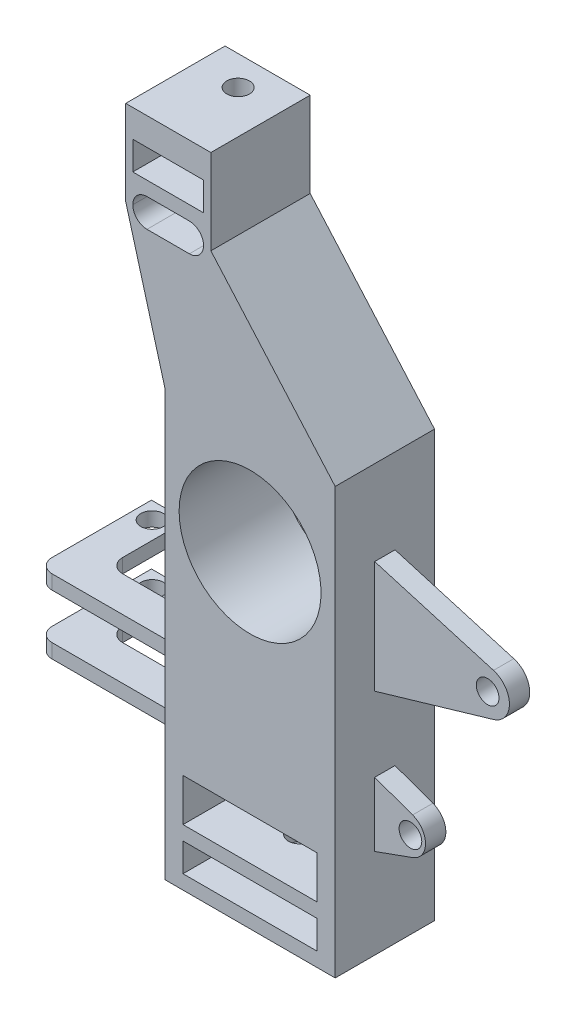
SolidWorks part; units mm, degrees
ref_plane "Front Plane" through (0, 0, 0) normal (0, 0, 1) x (1, 0, 0)
ref_plane "Top Plane" through (0, 0, 0) normal (0, 1, 0) x (1, 0, 0)
ref_plane "Right Plane" through (0, 0, 0) normal (1, 0, 0) x (0, 0, -1)
sketch "Sketch1" plane through (0, 0, 0) normal (0, 0, 1) x (1, 0, 0)
  line L3 (30, -10) -> (-30, -10)
  line L4 (0, 0) -> (0, 205)
  line L5 (0, 205) -> (-28.8109, 205) construction
  line L6 (-28.8109, 205) -> (0, 0) construction
  line L7 (30, -10) -> (30, 140)
  line L13 (-30, 140) -> (-30, -10)
  line L15 (-13.8109, 190) -> (-13.8109, 220)
  line L16 (-13.8109, 220) -> (-43.8109, 220)
  line L17 (-43.8109, 220) -> (-43.8109, 190)
  line L19 (-43.8109, 190) -> (-30, 140)
  line L20 (-13.8109, 190) -> (30, 140)
  dimension "D1" = 205
  dimension "D2" = 8
  dimension "D3" = 30
  dimension "D4" = 30
  dimension "D5" = 10
  dimension "D6" = 15
  dimension "D7" = 15
  dimension "D8" = 15
  dimension "D9" = 15
  dimension "D10" = 30
  dimension "D11" = 150
  dimension "D12" = 150
sketch "Sketch3" plane through (0, 0, 0) normal (1, 0, 0) x (0, 0, -1)
  line L0 (0, 205) -> (0, 0) construction
  line L1 (0, 205) -> (0, 0) construction
  line L2 (7.1588, 205) -> (0, 0) construction
  line L3 (0, 205) -> (7.1588, 205)
  dimension "D1" = 2
  dimension "D2" = 205
extrude "Boss-Extrude1" add sketch "Sketch1" along normal mid plane 35 contours L17 L19 L13 L3 L7 L20 L15 L16 region at (-4.5054, 93.3745, 0)
sketch "Sketch4" plane through (0, 0, 0) normal (0, 0, 1) x (1, 0, 0)
  line L0 (0, 205.3073) -> (-28.8541, 205.3073) construction
  line L1 (0, 205) -> (0, 0) construction
  line L2 (-28.8541, 205.3073) -> (0, 0) construction
  point P4 (0, 0)
  dimension "D1" = 8
sketch3d "3DSketch1"
  line L0 (0, 205, -7.1588) -> (-28.8601, 205, -7.1588) construction
  line L1 (-28.8601, 205, -7.1588) -> (-28.8265, 205.111, 0) construction
  line L2 (-28.8541, 205.3073, 0) -> (0, 0, 0) construction
  line L3 (0, 205, 0) -> (0, 205, -7.1588) construction
  line L4 (0, 205, -7.1588) -> (0, 0, 0) construction
  point P9 (0, 0, 0)
  point P10 (0, 0, 0)
  point P11 (0, 0, 0)
  point P12 (-28.8601, 205, -7.1588)
  point P13 (0, 0, 0)
sketch3d "3DSketch2"
  line L0 (-28.8601, 205, -7.1588) -> (0, 0, 0)
  point P4 (0, 0, 0)
sketch "Sketch6" plane through (0, 0, -17.5) normal (0, 0, -1) x (-1, 0, 0)
  line L0 (16.383, 195.3073) -> (41.3251, 195.3073)
  line L1 (23.6291, 5) -> (-23.6291, 5)
  line L2 (23.6291, 5) -> (23.6291, -5)
  line L3 (23.6291, -5) -> (-23.6291, -5)
  line L4 (-23.6291, 5) -> (-23.6291, -5)
  line L5 (23.6291, 5) -> (-23.6291, -5) construction
  line L6 (23.6291, -5) -> (-23.6291, 5) construction
  line L7 (23.6291, 25) -> (-23.6291, 25)
  line L8 (23.6291, 25) -> (23.6291, 10)
  line L9 (23.6291, 10) -> (-23.6291, 10)
  line L10 (-23.6291, 25) -> (-23.6291, 10)
  line L11 (23.6291, 25) -> (-23.6291, 10) construction
  line L12 (23.6291, 10) -> (-23.6291, 25) construction
  line L13 (41.3251, 210.3073) -> (16.383, 210.3073)
  line L14 (41.3251, 210.3073) -> (41.3251, 200.3073)
  line L15 (41.3251, 200.3073) -> (16.383, 200.3073)
  line L16 (16.383, 210.3073) -> (16.383, 200.3073)
  line L17 (41.3251, 210.3073) -> (16.383, 200.3073) construction
  line L18 (41.3251, 200.3073) -> (16.383, 210.3073) construction
  line L19 (41.3251, 195.3073) -> (41.3251, 185.3073)
  line L20 (41.3251, 185.3073) -> (16.383, 185.3073)
  line L21 (16.383, 185.3073) -> (16.383, 195.3073)
  point P0 (0, 0)
  point P6 (0, 17.5)
  point P11 (28.8541, 205.3073)
  dimension "D1" = 10
  dimension "D2" = 15
  dimension "D3" = 5
  dimension "D4" = 10
  dimension "D5" = 10
  dimension "D6" = 5
extrude "Cut-Extrude1" cut sketch "Sketch6" against normal through all
sketch "Sketch7" plane through (0, 0, -17.5) normal (0, 0, -1) x (-1, 0, 0)
  line L0 (0, 205) -> (0, 0) construction
  line L1 (-30, -10) -> (30, -10) construction
  circle A0 centre (0, 105) radius 25
  point P0 (0, 105)
  dimension "D2" = 50
  dimension "D1" = 115
extrude "Cut-Extrude2" cut sketch "Sketch7" against normal through all
sketch "Sketch8" plane through (0, 220, 0) normal (0, 1, 0) x (1, 0, 0)
  circle A0 centre (-28.8601, 7.1588) radius 4
  dimension "D1" = 8
extrude "Cut-Extrude3" cut sketch "Sketch8" against normal blind 30
sketch "Sketch10" plane through (0, -10, 0) normal (0, -1, 0) x (1, 0, 0)
  circle A0 centre (0, 0) radius 4
  dimension "D1" = 8
extrude "Cut-Extrude4" cut sketch "Sketch10" against normal blind 30
sketch "Sketch11" plane through (30, 0, 0) normal (1, 0, 0) x (0, 0, -1)
  line L1 (-3.5809, 110.12) -> (3.5794, 110.12)
  line L2 (-3.5809, 110.12) -> (-3.5809, 70.5679)
  line L3 (-3.5809, 70.5679) -> (3.5794, 70.5679)
  line L4 (3.5794, 110.12) -> (3.5794, 70.5679)
  line L5 (-3.5809, 44.2881) -> (3.5794, 44.2881)
  line L6 (-3.5809, 44.2881) -> (-3.5809, 21.6508)
  line L7 (-3.5809, 21.6508) -> (3.5794, 21.6508)
  line L8 (3.5794, 44.2881) -> (3.5794, 21.6508)
extrude "Boss-Extrude2" add sketch "Sketch11" along normal blind 50
sketch "Sketch12" plane through (0, 0, 3.5809) normal (0, 0, 1) x (1, 0, 0)
  line L0 (30, 90.3439) -> (80, 90.3439) construction
  line L1 (30, 110.12) -> (30, 70.5679) construction
  line L2 (80, 110.12) -> (80, 70.5679) construction
  line L3 (30, 32.9695) -> (80, 32.9695) construction
  line L4 (30, 44.2881) -> (30, 21.6508) construction
  line L5 (80, 44.2881) -> (80, 21.6508) construction
sketch "Sketch13" plane through (0, 0, 3.5809) normal (0, 0, 1) x (1, 0, 0)
  line L0 (30, 90.3439) -> (80, 90.3439) construction
  line L1 (30, 32.9695) -> (80, 32.9695) construction
  circle A0 centre (69.8025, 90.3439) radius 4
  circle A1 centre (42.5917, 32.9695) radius 4
  point P8 (42.5917, 32.9695)
  point P9 (68.013, 90.3439)
  dimension "D1" = 8
  dimension "D2" = 8
  dimension "D3" = 63.5
extrude "Cut-Extrude5" cut sketch "Sketch13" against normal blind 50
sketch "Sketch14" plane through (0, 0, 3.5809) normal (0, 0, 1) x (1, 0, 0)
  line L0 (30, 110.12) -> (71.8574, 97.8439)
  line L1 (30, 110.12) -> (80, 110.12)
  line L2 (71.8574, 82.8439) -> (30, 70.5679)
  line L3 (80, 110.12) -> (80, 70.5679)
  line L4 (80, 70.5679) -> (30, 70.5679)
  circle A0 centre (69.8025, 90.3439) radius 4 construction
  arc A1 (71.8574, 97.8439) -> (71.8574, 82.8439) centre (69.6578, 90.3439) cw
  dimension "D1" = 7.5
  dimension "D2" = 7.5
extrude "Cut-Extrude6" cut sketch "Sketch14" against normal blind 50
sketch "Sketch15" plane through (0, 0, 3.5809) normal (0, 0, 1) x (1, 0, 0)
  line L0 (30, 44.2881) -> (43.3495, 39.4695)
  line L1 (30, 44.2881) -> (80, 44.2881)
  line L2 (43.3495, 26.4695) -> (30, 21.6508)
  line L3 (80, 44.2881) -> (80, 21.6508)
  line L4 (80, 21.6508) -> (30, 21.6508)
  circle A0 centre (42.5917, 32.9695) radius 4 construction
  arc A1 (43.3495, 39.4695) -> (43.3495, 26.4695) centre (41.0032, 32.9695) cw
  dimension "D1" = 6.5
  dimension "D2" = 6.5
extrude "Cut-Extrude7" cut sketch "Sketch15" against normal blind 50
sketch3d "3DSketch3"
  point P0 (-85, 34, -33)
  point P1 (0, 0, 0)
  point P2 (0, 0, 0)
  point P3 (0, 0, 0)
  point P4 (0, 0, 0)
  point P5 (0, 0, 0)
  point P6 (0, 0, 0)
  point P7 (0, 0, 0)
  point P8 (-71.3835, 94.2445, 58.1078)
  point P9 (-86.3356, 90.1515, 16.2639)
  point P10 (-86.3356, 74.7555, 5.9999)
  point P11 (-57.4855, 80.2, 14.0614)
  point P12 (-57.8502, 78.7732, 5.313)
  point P13 (0, 0, 0)
  point P14 (0, 0, 0)
  point P15 (0, 0, 0)
  point P16 (0, 0, 0)
  point P18 (0, 0, 0)
  point P19 (0, 0, 0)
  point P20 (0, 0, 0)
  point P21 (0, 0, 0)
  point P22 (0, 0, 0)
  point P23 (0, 0, 0)
sketch "Sketch18" plane through (-30, 0, 0) normal (-1, 0, 0) x (0, 0, 1)
  line L0 (-33, 34) -> (22.4569, 34) construction
  line L1 (0, 205) -> (0, 0) construction
  line L2 (11.6727, 47) -> (-11.6727, 47)
  line L3 (11.6727, 47) -> (11.6727, 42)
  line L4 (11.6727, 42) -> (-11.6727, 42)
  line L6 (11.6727, 47) -> (-11.6727, 42) construction
  line L7 (11.6727, 42) -> (-11.6727, 47) construction
  line L8 (-11.6727, 26) -> (-38.9523, 26)
  line L9 (11.6727, 26) -> (-11.6727, 26)
  line L10 (11.6727, 26) -> (11.6727, 21)
  line L11 (11.6727, 21) -> (-11.6727, 21)
  line L13 (11.6727, 26) -> (-11.6727, 21) construction
  line L14 (11.6727, 21) -> (-11.6727, 26) construction
  line L15 (-38.9523, 26) -> (-38.9523, 21)
  line L16 (-38.9523, 21) -> (-11.6727, 21)
  line L17 (-11.6727, 47) -> (-38.9523, 47)
  line L18 (-38.9523, 47) -> (-38.9523, 42)
  line L19 (-38.9523, 42) -> (-11.6727, 42)
  point P3 (0, 44.5)
  point P10 (0, 23.5)
  dimension "D1" = 8
  dimension "D2" = 8
  dimension "D3" = 5
  dimension "D4" = 5
extrude "Boss-Extrude3" add sketch "Sketch18" along normal blind 70
sketch "Sketch19" plane through (0, 47, 0) normal (0, 1, 0) x (1, 0, 0)
  circle A0 centre (-85, 33) radius 4
  dimension "D1" = 8
extrude "Cut-Extrude8" cut sketch "Sketch19" against normal blind 70
sketch "Sketch20" plane through (0, 21, 0) normal (0, -1, 0) x (1, 0, 0)
  line L0 (-78.7742, -38.9523) -> (-78.7742, -11.3955)
  line L1 (-100, -38.9523) -> (-30, -38.9523) construction
  line L2 (-78.7742, -11.3955) -> (-30, -11.3955)
  line L3 (-30, -17.5) -> (-30, 11.6727) construction
  line L4 (-30, -11.3955) -> (-30, -38.9523)
  line L5 (-30, -38.9523) -> (-78.7742, -38.9523)
extrude "Cut-Extrude9" cut sketch "Sketch20" against normal blind 70
sketch "Sketch22" plane through (0, 21, 0) normal (0, -1, 0) x (1, 0, 0)
  line L0 (-91.2054, -38.9523) -> (-91.2054, 1.0345)
  line L1 (-100, -38.9523) -> (-78.7742, -38.9523) construction
  line L2 (-91.2054, 1.0345) -> (-30, 1.0345)
  line L3 (-30, 17.5) -> (-30, -17.5) construction
  line L4 (-91.2054, -38.9523) -> (-100, -38.9523)
  line L5 (-100, -38.9523) -> (-100, 11.6727)
  line L6 (-100, 11.6727) -> (-30, 11.6727)
  line L7 (-30, 11.6727) -> (-30, 1.0345)
  dimension "D1" = 12.43
extrude "Cut-Extrude10" cut sketch "Sketch22" against normal blind 70
fillet "Fillet1" radius 5 1 edges at (-78.7742, 44.5, -11.3955)
fillet "Fillet2" radius 5 1 edges at (-78.7742, 23.5, -11.3955)
fillet "Fillet3" radius 5 2 edges at (-91.2054, 23.5, 1.0345) (-91.2054, 44.5, 1.0345)
fillet "Fillet4" radius 5 4 edges at (-41.3251, 185.3073, 0) (-16.383, 185.3073, 0) (-16.383, 195.3073, 0) (-41.3251, 195.3073, 0)
